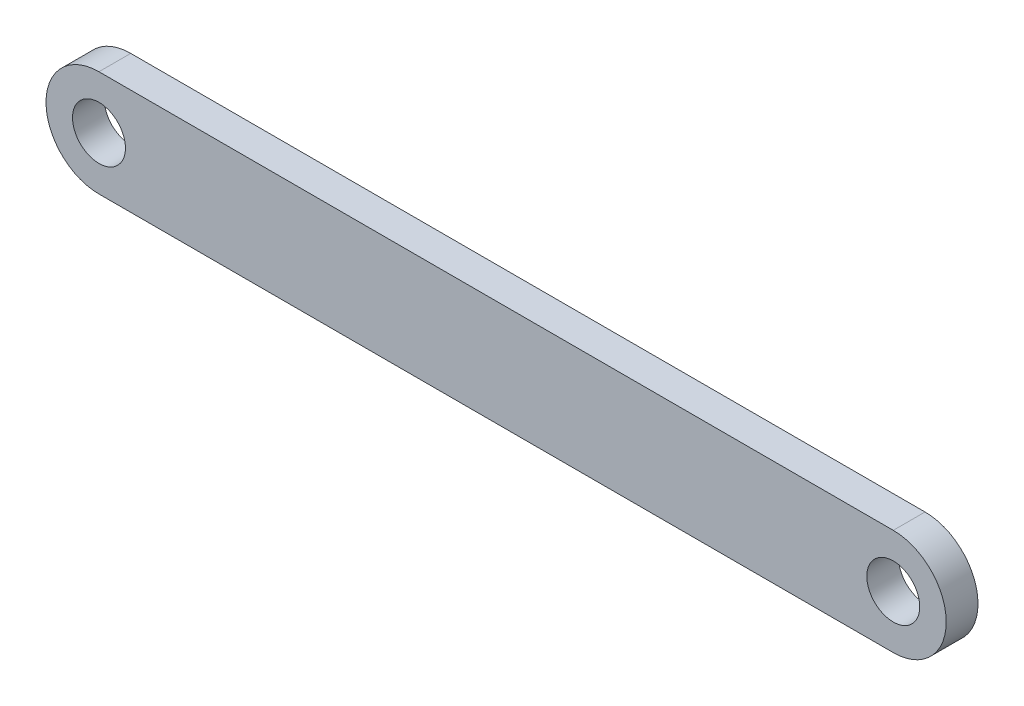
SolidWorks part; units mm, degrees
ref_plane "Front Plane" through (0, 0, 0) normal (0, 0, 1) x (1, 0, 0)
ref_plane "Top Plane" through (0, 0, 0) normal (0, 1, 0) x (1, 0, 0)
ref_plane "Right Plane" through (0, 0, 0) normal (1, 0, 0) x (0, 0, -1)
sketch "Sketch1" plane through (0, 0, 0) normal (0, 0, 1) x (1, 0, 0)
  line L1 (120.0787, 190.0323) -> (195.0787, 190.0323)
  line L3 (120.0787, 200.0323) -> (195.0787, 200.0323)
  arc A0 (120.0787, 200.0323) -> (120.0787, 190.0323) centre (120.0787, 195.0323) ccw
  arc A1 (195.0787, 200.0323) -> (195.0787, 190.0323) centre (195.0787, 195.0323) cw
  circle A2 centre (120.0787, 195.0323) radius 2.5
  circle A3 centre (195.0787, 195.0323) radius 2.5
  dimension "D3" = 5
  dimension "D4" = 5
  dimension "D1" = 75
  dimension "D2" = 10
extrude "Boss-Extrude1" add sketch "Sketch1" along normal blind 3
